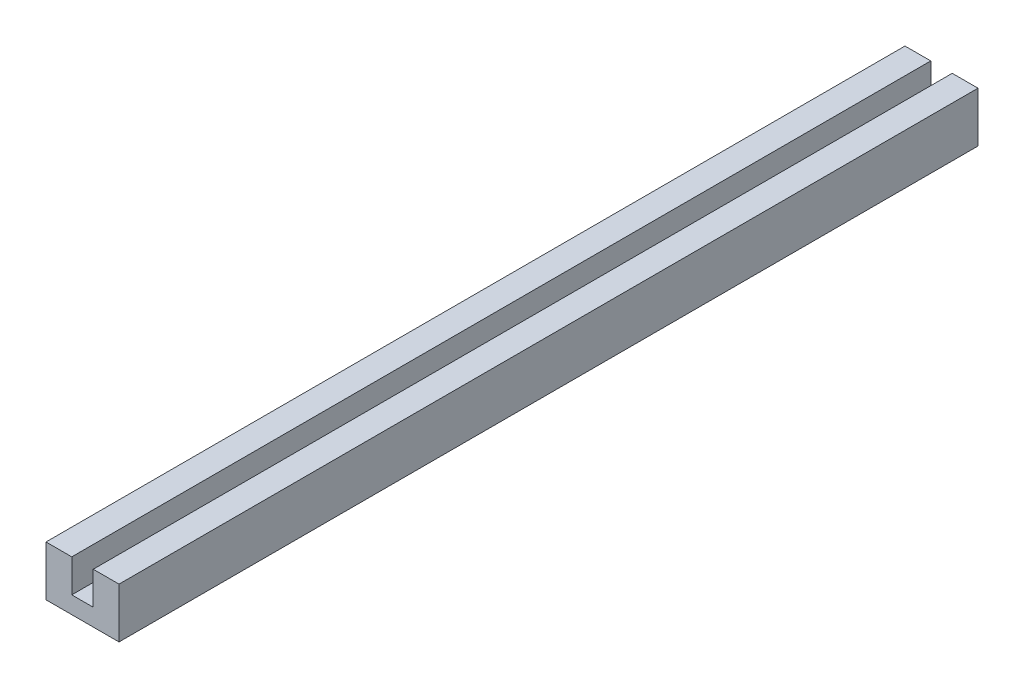
SolidWorks part; units mm, degrees
ref_plane "Front Plane" through (0, 0, 0) normal (0, 0, 1) x (1, 0, 0)
ref_plane "Top Plane" through (0, 0, 0) normal (0, 1, 0) x (1, 0, 0)
ref_plane "Right Plane" through (0, 0, 0) normal (1, 0, 0) x (0, 0, -1)
sketch "Sketch2" plane through (0, 0, 0) normal (0, 0, 1) x (1, 0, 0)
  line L0 (0, 0) -> (5.1, 0)
  line L1 (5.1, 0) -> (5.1, 3.5)
  line L2 (5.1, 3.5) -> (3.3, 3.5)
  line L3 (3.3, 3.5) -> (3.3, 1.2)
  line L4 (3.3, 1.2) -> (1.8, 1.2)
  line L5 (1.8, 1.2) -> (1.8, 3.5)
  line L6 (1.8, 3.5) -> (0, 3.5)
  line L7 (0, 3.5) -> (0, 0)
  dimension "D1" = 1.5
  dimension "D2" = 3.5
  dimension "D3" = 1.2
  dimension "D4" = 1.8
extrude "Boss-Extrude1" add sketch "Sketch2" along normal blind 60 contours L4 L5 L6 L7 L0 L1 L2 L3
equation "\"PCBThickness\"= 1.5"
equation "\"RailThickness\"= 1.25"
equation "\"RailDepth\"= 3.5"
